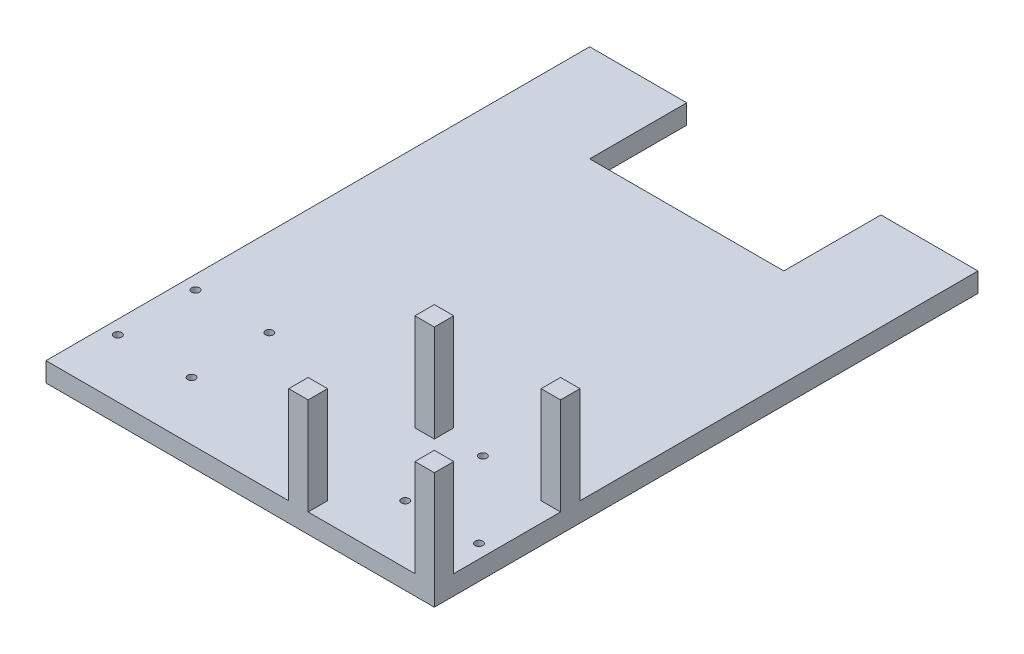
SolidWorks part; units mm, degrees
material "Pine"
ref_plane "Front Plane" through (0, 0, 0) normal (0, 0, 1) x (1, 0, 0)
ref_plane "Top Plane" through (0, 0, 0) normal (0, 1, 0) x (1, 0, 0)
ref_plane "Right Plane" through (0, 0, 0) normal (1, 0, 0) x (0, 0, -1)
sketch "Sketch3" plane through (0, 0, 0) normal (0, 1, 0) x (1, 0, 0)
  line L1 (-100, -140) -> (100, -140)
  line L2 (-100, -140) -> (-100, 140)
  line L3 (-100, 140) -> (100, 140)
  line L4 (100, -140) -> (100, 140)
  line L5 (-100, -140) -> (100, 140) construction
  line L6 (-100, 140) -> (100, -140) construction
  point P0 (0, 0)
  dimension "D1" = 200
  dimension "D2" = 280
extrude "Boss-Extrude1" add sketch "Sketch3" along normal blind 10
sketch "Sketch4" plane through (0, 10, 0) normal (0, 1, 0) x (1, 0, 0)
  line L0 (100, -140) -> (100, 140) construction
  line L1 (100, -140) -> (90, -140)
  line L2 (100, -140) -> (100, -130)
  line L3 (100, -65) -> (90, -65)
  line L4 (25, -140) -> (25, -130)
  line L5 (-100, -140) -> (100, -140) construction
  line L6 (35, -140) -> (35, -130)
  line L7 (90, -65) -> (90, -75)
  line L8 (35, -65) -> (25, -65)
  line L9 (35, -140) -> (25, -140)
  line L10 (25, -130) -> (35, -130)
  line L11 (25, -75) -> (35, -75)
  line L12 (90, -75) -> (100, -75)
  line L13 (90, -130) -> (100, -130)
  line L14 (25, -75) -> (25, -65)
  line L15 (35, -75) -> (35, -65)
  line L16 (90, -130) -> (90, -140)
  line L17 (100, -75) -> (100, -65)
  point P20 (95, -130)
  dimension "D1" = 0
  dimension "D2" = 0
  dimension "D3" = 75
  dimension "D4" = 75
  dimension "D5" = 10
  dimension "D6" = 10
  dimension "D7" = 10
  dimension "D8" = 10
  dimension "D9" = 10
extrude "Boss-Extrude2" add sketch "Sketch4" along normal blind 50
sketch "Sketch7" plane through (0, 0, 0) normal (0, -1, 0) x (1, 0, 0)
  line L0 (100, 140) -> (100, -140) construction
  line L1 (-100, 140) -> (100, 140) construction
  line L4 (-93, 70) -> (93, 70) construction
  line L5 (-93, 110) -> (93, 110) construction
  line L6 (-100, -140) -> (-100, 140) construction
  circle A8 centre (-93, 70) radius 2
  circle A9 centre (-93, 110) radius 2
  circle A10 centre (-55, 110) radius 2
  circle A11 centre (-55, 70) radius 2
  circle A12 centre (55, 110) radius 2
  circle A13 centre (93, 110) radius 2
  circle A14 centre (93, 70) radius 2
  circle A15 centre (55, 70) radius 2
  dimension "D17" = 40
  dimension "D4" = 7
  dimension "D1" = 38
  dimension "D2" = 40
  dimension "D3" = 38
  dimension "D5" = 38
  dimension "D6" = 40
  dimension "D7" = 38
  dimension "D16" = 7
  dimension "D18" = 55.1725
  dimension "D19" = 40
  dimension "D20" = 55.1725
  dimension "D27" = 30
extrude "Cut-Extrude2" cut sketch "Sketch7" against normal blind 10
sketch "Sketch8" plane through (0, 10, 0) normal (0, 1, 0) x (1, 0, 0)
  line L0 (-100, -140) -> (25, -140) construction
  line L1 (-100, 140) -> (-100, -140) construction
  line L2 (100, -65) -> (100, 140) construction
  circle A0 centre (-35, -35) radius 4
  circle A1 centre (-15, -35) radius 4
  circle A5 centre (-35, 40) radius 4
  circle A6 centre (-15, 40) radius 4
  circle A7 centre (45, 2.5) radius 4
  circle A8 centre (65, 2.5) radius 4
  dimension "D1" = 8
  dimension "D2" = 8
  dimension "D4" = 8
  dimension "D5" = 8
  dimension "D7" = 8
  dimension "D8" = 8
  dimension "D3" = 20
  dimension "D6" = 20
  dimension "D9" = 20
  dimension "D10" = 105
  dimension "D11" = 65
  dimension "D12" = 65
  dimension "D13" = 75
  dimension "D14" = 37.5
  dimension "D15" = 35
extrude "Cut-Extrude3" [suppressed] cut sketch "Sketch8" against normal blind 10
sketch "Sketch9" plane through (0, 10, 0) normal (0, 1, 0) x (1, 0, 0)
  line L0 (100, 140) -> (-100, 140) construction
  line L1 (50, 140) -> (-50, 140)
  line L2 (50, 140) -> (50, 90)
  line L3 (50, 90) -> (-50, 90)
  line L4 (-50, 140) -> (-50, 90)
  line L5 (50, 98.4245) -> (100, 98.4245) construction
  line L6 (100, -65) -> (100, 140) construction
  line L7 (-50, 98.4245) -> (-100, 98.4245) construction
  line L8 (-100, 140) -> (-100, -140) construction
  dimension "D1" = 100
  dimension "D2" = 50
extrude "Cut-Extrude4" cut sketch "Sketch9" against normal blind 10
